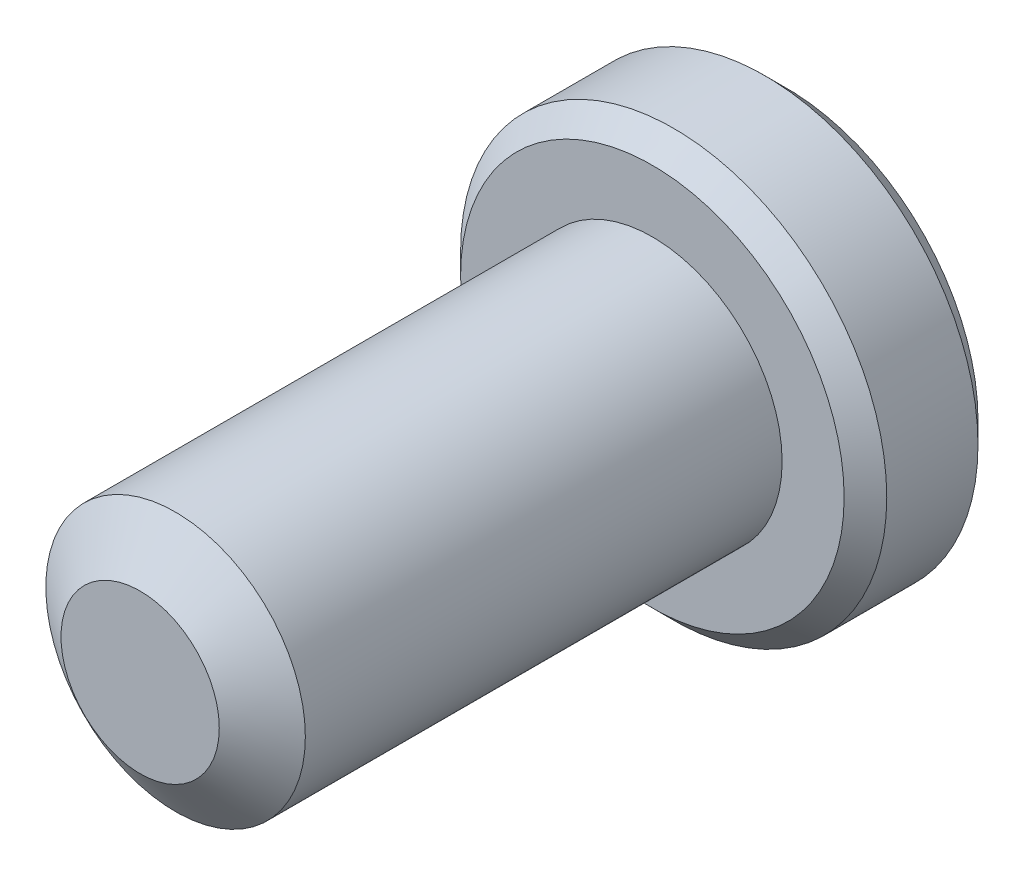
SolidWorks part; units mm, degrees
ref_plane "Front Plane" through (0, 0, 0) normal (0, 0, 1) x (1, 0, 0)
ref_plane "Top Plane" through (0, 0, 0) normal (0, 1, 0) x (1, 0, 0)
ref_plane "Right Plane" through (0, 0, 0) normal (1, 0, 0) x (0, 0, -1)
sketch "Sketch1" plane through (0, 0, 0) normal (0, 0, 1) x (1, 0, 0)
  circle A0 centre (0, 0) radius 2.413
  dimension "OD" = 4.826
extrude "Extrude1" add sketch "Sketch1" against normal blind 9.525
sketch "Sketch2" plane through (0, 0, 0) normal (0, 0, 1) x (1, 0, 0)
  circle A0 centre (0, 0) radius 2.413 construction
  circle A1 centre (0, 0) radius 2.413
curve "Helix/Spiral1" pitch 1.0583 height 10.5833 turns 10 parameters "pitch"=1.0583
sketch "Sketch3" plane through (0, 0, 0) normal (1, 0, 0) x (0, 0, -1)
  line L0 (-0.926, 2.413) -> (-0.5292, 1.7256)
  line L1 (-0.5292, 1.7256) -> (-0.3969, 1.7256)
  line L2 (-0.3969, 1.7256) -> (0, 2.413)
  line L3 (-0.926, 2.413) -> (0, 2.413)
  line L4 (-0.463, 2.413) -> (-0.463, 1.7256) construction
  line L5 (-0.7276, 2.0693) -> (-0.1984, 2.0693) construction
  line L6 (0, 2.413) -> (0, -2.413) construction
  dimension "D1" = 0.1323
  dimension "D2" = 0.5292
  dimension "D3" = 60
sweep "Cut-Sweep1" [suppressed] cut profiles "Sketch3" path "Helix/Spiral1"
sketch "Sketch4" plane through (0, 0, 0) normal (1, 0, 0) x (0, 0, -1)
  line L0 (0.6592, 2.413) -> (0, 1.4716)
  line L1 (0, 1.4716) -> (0, 2.413)
  line L2 (0.6592, 2.413) -> (0, 2.413)
  line L3 (-0.926, 2.413) -> (0, 2.413) construction
  line L4 (0, 0) -> (7.0209, 0) construction
  dimension "D1" = 55
  dimension "D2" = 0.254
revolve "Cut-Revolve1" cut sketch "Sketch4" angle 360 about L4
sketch "Sketch6" plane through (0, 0, -9.525) normal (0, 0, -1) x (-1, 0, 0)
  circle A0 centre (0, 0) radius 3.9624
  dimension "head dia" = 7.9248
extrude "Extrude2" add sketch "Sketch6" along normal blind 2.4892
sketch "Sketch7" plane through (0, 0, -12.0142) normal (0, 0, -1) x (-1, 0, 0)
  line L1 (0, 1.3748) -> (-1.1906, 0.6874)
  line L2 (-1.1906, 0.6874) -> (-1.1906, -0.6874)
  line L3 (-1.1906, -0.6874) -> (0, -1.3748)
  line L4 (0, -1.3748) -> (1.1906, -0.6874)
  line L5 (1.1906, -0.6874) -> (1.1906, 0.6874)
  line L6 (1.1906, 0.6874) -> (0, 1.3748)
  circle A0 centre (0, 0) radius 1.1906 construction
  dimension "hex dia" = 2.3813
extrude "Cut-Extrude1" cut sketch "Sketch7" against normal blind 1.7859
sketch "Sketch8" plane through (0, 0, -12.0142) normal (0, 0, -1) x (-1, 0, 0)
  circle A0 centre (0, 0) radius 1.3748
extrude "Cut-Extrude2" cut sketch "Sketch8" against normal through all draft 45
chamfer "Chamfer1" distance 0.3962 angle 45 2 edges at (-3.9624, 0, -12.0142) (-3.9624, 0, -9.525)
sketch "Sketch10" plane through (0, 0, -9.525) normal (0, 0, 1) x (1, 0, 0)
  circle A1 centre (0, 0) radius 2.413
  circle A2 centre (0, 0) radius 2.413
  dimension "D1" = 0
ref_plane "Plane1" through (0, 0, 0) normal (0, 0, 1) x (1, 0, 0)
extrude "partial thread" [suppressed] add sketch "Sketch10" along normal up to surface (12.7 mm away) separate body up to plane "Plane1"
chamfer "Chamfer2" [suppressed] distance 0.0965 angle 45
combine bodies "Combine1" [suppressed] operation type add bodies to combine 107 108
sketch "Sketch9" plane through (0, 0, 0) normal (1, 0, 0) x (0, 0, -1)
  line L0 (0, 2.413) -> (0, -2.413) construction
  line L1 (2.6458, 2.413) -> (2.6458, -2.413) construction
  dimension "D1" = 2.6458
sketch "Sketch11" plane through (0, 0, -9.525) normal (0, 0, 1) x (1, 0, 0)
  circle A0 centre (0, 0) radius 3.175
  dimension "Shoulder Diameter" = 6.35
equation "\"D3@Helix/Spiral1\" = \"screw length@Extrude1\"+\"pitch@Helix/Spiral1\""
equation "\"D1@Sketch3\" = \"pitch@Helix/Spiral1\"*.125"
equation "\"D2@Sketch3\" = \"pitch@Helix/Spiral1\"*.5"
equation "\"D1@Cut-Extrude1\" = \"hex dia@Sketch7\"*.75"
equation "\"D1@Chamfer1\" = \"head dia@Sketch6\"*.05"
equation "\"D1@Sketch9\" = \"pitch@Helix/Spiral1\"*2.5"
equation "\"D1@Chamfer2\"=\"OD@Sketch1\"*.02"
